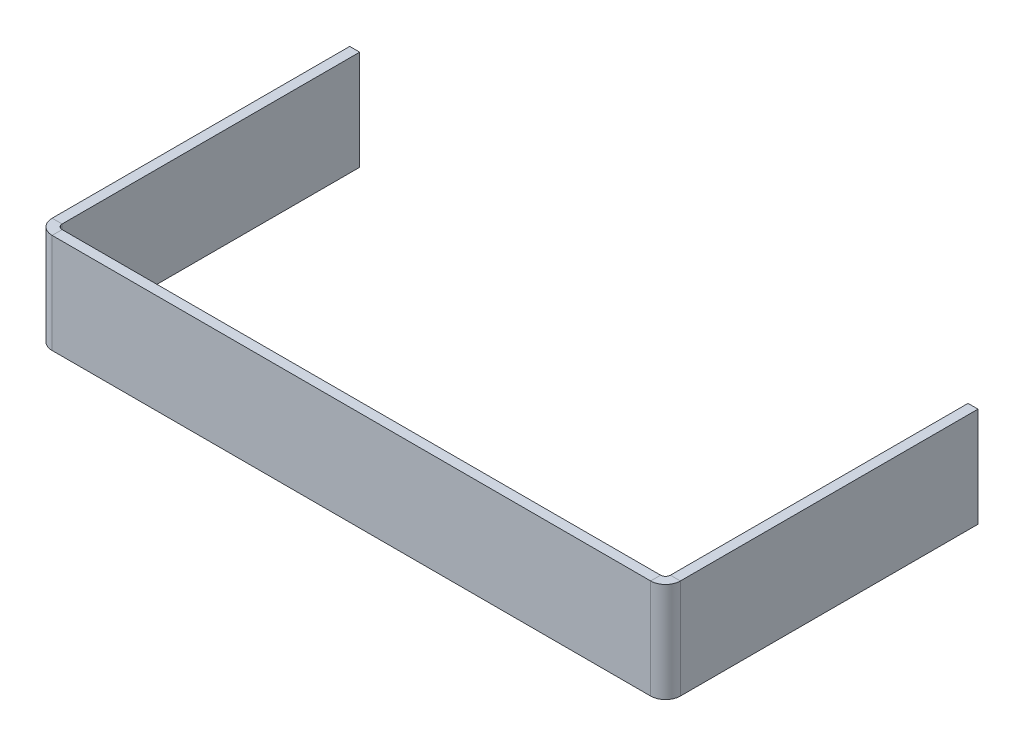
SolidWorks part; units mm, degrees
note: The reader was unsure of these and kept them because the rebuilt part matched: flange length of "Edge-Flange1", "Edge-Flange2".
ref_plane "Front Plane" through (0, 0, 0) normal (0, 0, 1) x (1, 0, 0)
ref_plane "Top Plane" through (0, 0, 0) normal (0, 1, 0) x (1, 0, 0)
ref_plane "Right Plane" through (0, 0, 0) normal (1, 0, 0) x (0, 0, -1)
sketch "Sketch1" plane through (0, 0, 0) normal (0, 0, 1) x (1, 0, 0)
  line L0 (79, 0) -> (87.3067, 0) construction
  line L1 (79, 0) -> (70.8519, 0) construction
  line L2 (-79, 0) -> (-18, 0) construction
  line L3 (75, 2.5) -> (75, 9.5) construction
  line L5 (75, 0) -> (76.6898, 0)
  line L6 (75, 0) -> (75, 15)
  line L7 (75, 2.5) -> (75, -6.9309) construction
  line L9 (76.6898, 0) -> (76.6898, 15)
  line L10 (75, 15) -> (76.6898, 15)
  point P2 (75, 0)
  dimension "D1" = 15
sketch "Sketch2" plane through (0, 0, 0) normal (0, 1, 0) x (1, 0, 0)
  line L0 (75, 0) -> (75, -41.5)
  line L1 (73.5, -43) -> (-16.5, -43)
  line L2 (-18, -41.5) -> (-18, 4)
  line L3 (20, 4) -> (-35, 4) construction
  arc A0 (-16.5, -43) -> (-18, -41.5) centre (-16.5, -41.5) cw
  arc A1 (73.5, -43) -> (75, -41.5) centre (73.5, -41.5) ccw
  dimension "D1" = 1.5
  dimension "D2" = 1.5
  dimension "D3" = 90
  dimension "D4" = 47
ref_plane "Plane1" through (75, 0, 0) normal (-1, 0, 0) x (0, 0, 1)
sketch "Sketch3" plane through (75, 0, 0) normal (-1, 0, 0) x (0, 0, 1)
  line L0 (0, 15) -> (0, 0) construction
  line L1 (0, 15) -> (41.5, 15)
  line L3 (0, 0) -> (41.5, 0)
  line L4 (41.5, 15) -> (41.5, 0)
  line L5 (0, 15) -> (-4, 15)
  line L6 (-4, 15) -> (-4, 0)
  line L7 (0, 0) -> (-4, 0)
  dimension "D1" = 4
base flange "Base-Flange1" sketch "Sketch3" thickness 1.5 reverse thickness direction no parameters "D1"=0.7366
edge flange "Edge-Flange1" sketch "Sketch10" flange angle 90 flange length 93 flange position material outside bend radius 0.7366 thickness 1.5 relief rectangular parameters "D6"=10
sketch "Sketch10" plane through (75, 0, 41.5) normal (0, 0, 1) x (0, 1, 0)
  line L0 (0, 0) -> (15, 0) construction
  line L1 (0, 0) -> (15, 0)
  line L2 (0, 0) -> (0, 91.5)
  line L3 (0, 91.5) -> (15, 91.5)
  line L4 (15, 91.5) -> (15, 0)
bend "EdgeBend1" bend radius 0.7366 bend angle 90 parameters "D5"=1
edge flange "Edge-Flange2" sketch "Sketch13" flange angle 90 flange length 47 flange position material outside bend radius 0.7366 thickness 1.5 relief rectangular parameters "D6"=10
sketch "Sketch13" plane through (-16.5, 0, 41.5) normal (-1, 0, 0) x (0, 1, 0)
  line L0 (15, 0) -> (0, 0) construction
  line L1 (15, 0) -> (0, 0)
  line L2 (0, 0) -> (0, 45.5)
  line L3 (0, 45.5) -> (15, 45.5)
  line L4 (15, 45.5) -> (15, 0)
bend "EdgeBend2" bend radius 0.7366 bend angle 90 parameters "D5"=2
unfold "Unfold1" [suppressed]
sketch "Bend-Lines1" [suppressed] plane through (0, 0, 0) normal (0, 1, 0) x (1, 0, 0)
sketch "Bounding-Box1" [suppressed] plane through (0, 0, 0) normal (0, 1, 0) x (1, 0, 0)
sheet metal parameters "Sheet-Metal2" thickness 1.5 parameters "D1"=0.7366
flat pattern "Flat-Pattern2"
sketch "Bend-Lines2" plane through (0, 0, 0) normal (0, 1, 0) x (1, 0, 0)
sketch3d "Bounding-Box2" [suppressed]
  line L0 (0, 0, 0) -> (-41.5, 0, 0) construction
  line L1 (0, 15, 0) -> (-41.5, 15, 0) construction
  line L2 (0, 0, 0) -> (0, 15, 0) construction
  line L3 (-41.5, 0, 0) -> (-41.5, 15, 0) construction
sheet metal parameters "Sheet-Metal3" thickness 1.5 parameters "D1"=0.7366
flat pattern "Flat-Pattern2"
sketch "Bend-Lines2" plane through (75, 0, 0) normal (-1, 0, 0) x (0, 0, 1)
  line L0 (41.931, 0) -> (41.931, 15) construction
  line L1 (41.931, 0) -> (41.931, 15) construction
sketch3d "Bounding-Box2" [suppressed]
  line L0 (0, 0, 0) -> (133.8619, 0, 0) construction
  line L1 (0, 15, 0) -> (133.8619, 15, 0) construction
  line L2 (0, 0, 0) -> (0, 15, 0) construction
  line L3 (133.8619, 0, 0) -> (133.8619, 15, 0) construction
bend of the flat pattern "Flatten-<EdgeBend1>1"
sheet metal parameters "Sheet-Metal4" thickness 1.5 parameters "D1"=0.7366
flat pattern "Flat-Pattern2"
sketch "Bend-Lines2" plane through (75, 0, 0) normal (-1, 0, 0) x (0, 0, 1)
  line L0 (41.931, 0) -> (41.931, 15) construction
  line L1 (41.931, 0) -> (41.931, 15) construction
  line L2 (134.2929, 0) -> (134.2929, 15) construction
  line L3 (134.2929, 0) -> (134.2929, 15) construction
sketch3d "Bounding-Box2" [suppressed]
  line L0 (-4, 0, 0) -> (180.2239, 0, 0) construction
  line L1 (-4, 15, 0) -> (180.2239, 15, 0) construction
  line L2 (-4, 0, 0) -> (-4, 15, 0) construction
  line L3 (180.2239, 0, 0) -> (180.2239, 15, 0) construction
bend of the flat pattern "Flatten-<EdgeBend1>1"
bend of the flat pattern "Flatten-<EdgeBend2>1"
